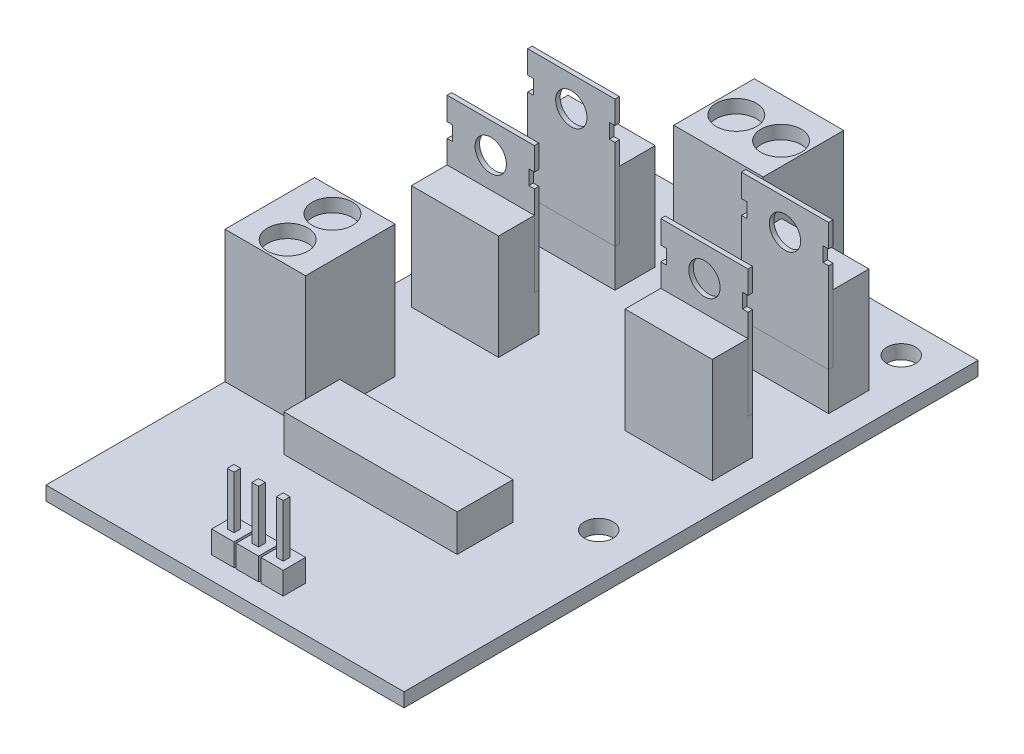
SolidWorks part; units mm, degrees
ref_plane "Front Plane" through (0, 0, 0) normal (0, 0, 1) x (1, 0, 0)
ref_plane "Top Plane" through (0, 0, 0) normal (0, 1, 0) x (1, 0, 0)
ref_plane "Right Plane" through (0, 0, 0) normal (1, 0, 0) x (0, 0, -1)
sketch "Sketch1" plane through (0, 0, 0) normal (0, 1, 0) x (1, 0, 0)
  line L1 (20.32, -32.5755) -> (-20.32, -32.5755)
  line L2 (20.32, -32.5755) -> (20.32, 32.5755)
  line L3 (20.32, 32.5755) -> (-20.32, 32.5755)
  line L4 (-20.32, -32.5755) -> (-20.32, 32.5755)
  line L5 (20.32, -32.5755) -> (-20.32, 32.5755) construction
  line L6 (20.32, 32.5755) -> (-20.32, -32.5755) construction
  point P0 (0, 0)
  dimension "D1" = 40.64
  dimension "D2" = 65.151
extrude "Boss-Extrude1" add sketch "Sketch1" along normal blind 1.5875
sketch "Sketch2" plane through (0, 1.5875, 0) normal (0, 1, 0) x (1, 0, 0)
  line L0 (20.32, 32.5755) -> (-20.32, 32.5755) construction
  line L1 (20.32, -32.5755) -> (20.32, 32.5755) construction
  circle A0 centre (-15.0114, 28.7147) radius 1.6256
  circle A1 centre (15.4686, 28.7147) radius 1.6256
  circle A2 centre (15.4686, -5.6261) radius 1.6256
  dimension "D1" = 30.48
  dimension "D2" = 2.2352
  dimension "D3" = 3.2512
  dimension "D4" = 3.2258
  dimension "D5" = 34.3408
extrude "Cut-Extrude1" cut sketch "Sketch2" against normal through all
sketch "Sketch3" plane through (0, 1.5875, 0) normal (0, 1, 0) x (1, 0, 0)
  line L0 (-5.08, 32.5755) -> (0, 23.4315) construction
  line L1 (-5.08, 32.5755) -> (5.08, 32.5755)
  line L2 (-5.08, 32.5755) -> (-5.08, 23.4315)
  line L3 (-5.08, 23.4315) -> (5.08, 23.4315)
  line L4 (5.08, 32.5755) -> (5.08, 23.4315)
  line L5 (0, 23.4315) -> (5.08, 32.5755) construction
  line L6 (20.32, 32.5755) -> (-20.32, 32.5755) construction
  line L7 (-20.32, 32.5755) -> (-20.32, -32.5755) construction
  line L8 (-20.32, -2.0955) -> (-11.176, -2.0955)
  line L9 (-20.32, -2.0955) -> (-20.32, -12.2555)
  line L10 (-20.32, -12.2555) -> (-11.176, -12.2555)
  line L11 (-11.176, -2.0955) -> (-11.176, -12.2555)
  line L12 (-20.32, -2.0955) -> (-11.176, -7.1755) construction
  line L13 (-11.176, -7.1755) -> (-20.32, -12.2555) construction
  line L14 (-20.32, -32.5755) -> (20.32, -32.5755) construction
  circle A0 centre (-2.54, 28.0035) radius 2.286
  circle A1 centre (2.54, 28.0035) radius 2.286
  circle A2 centre (-15.748, -4.6355) radius 2.286
  circle A3 centre (-15.748, -9.7155) radius 2.286
  line M4 (-20.32, 32.5755) -> (-20.32, -32.5755)
  line M7 (20.32, 32.5755) -> (-20.32, 32.5755)
  dimension "D3" = 4.572
  dimension "D1" = 10.16
  dimension "D2" = 9.144
  dimension "D4" = 20.32
extrude "Boss-Extrude2" add sketch "Sketch3" along normal blind 14.986 separate body contours A2 | L11 L8 L10 A3 A2 M4 | A3 | L4 L2 L3 A1 A0 M7 | A1 | A0 region at (0, 1.5875, -28.0035) region at (-15.748, 1.5875, 7.1755) region at (-2.54, 1.5875, -28.0035) region at (2.54, 1.5875, -28.0035) region at (-15.748, 1.5875, 4.6355) region at (-15.748, 1.5875, 9.7155)
extrude "Cut-Extrude2" cut sketch "Sketch3<3>" against normal blind 1.524 from vertex contours A3 | A2 | A1 | A0 region at (-2.54, 1.5875, -28.0035) region at (2.54, 1.5875, -28.0035) region at (-15.748, 1.5875, 4.6355) region at (-15.748, 1.5875, 9.7155) starting at point (-5.08, 16.5735, -32.5755)
sketch "Sketch3<3>" plane through (0, 1.5875, 0) normal (0, 1, 0) x (1, 0, 0) same geometry as "Sketch3"
sketch "Sketch4" plane through (0, 1.5875, 0) normal (0, 1, 0) x (1, 0, 0)
  line L0 (-7.1755, 23.4315) -> (7.1755, 23.4315) construction
  line L1 (17.0815, 23.4315) -> (7.1755, 23.4315)
  line L2 (17.0815, 23.4315) -> (17.0815, 18.8595)
  line L3 (17.0815, 18.8595) -> (7.1755, 18.8595)
  line L4 (7.1755, 23.4315) -> (7.1755, 18.8595)
  line L5 (17.0815, 5.6515) -> (7.1755, 5.6515)
  line L6 (17.0815, 5.6515) -> (17.0815, 10.2235)
  line L7 (17.0815, 10.2235) -> (7.1755, 10.2235)
  line L8 (7.1755, 5.6515) -> (7.1755, 10.2235)
  line L9 (-17.0815, 5.6515) -> (-7.1755, 5.6515)
  line L10 (-17.0815, 5.6515) -> (-17.0815, 10.2235)
  line L11 (-17.0815, 10.2235) -> (-7.1755, 10.2235)
  line L12 (-7.1755, 5.6515) -> (-7.1755, 10.2235)
  line L13 (-17.0815, 23.4315) -> (-7.1755, 23.4315)
  line L14 (-17.0815, 23.4315) -> (-17.0815, 18.8595)
  line L15 (-17.0815, 18.8595) -> (-7.1755, 18.8595)
  line L16 (-7.1755, 23.4315) -> (-7.1755, 18.8595)
  line L17 (-5.08, 23.4315) -> (5.08, 23.4315) construction
  line L18 (-7.1755, 18.8595) -> (7.1755, 10.2235) construction
  point P16 (0, 23.4315)
  point P20 (0, 14.5415)
  dimension "D1" = 4.572
  dimension "D2" = 9.906
  dimension "D3" = 8.636
  dimension "D4" = 14.351
extrude "Boss-Extrude3" add sketch "Sketch4" along normal blind 11.938 separate body contours L16 L13 L14 L15 region at (-12.1285, 1.5875, -21.1455)
sketch "Sketch5" plane through (0, 0, -18.8595) normal (0, 0, 1) x (1, 0, 0)
  line L0 (-7.1755, 13.5255) -> (-7.1755, 1.5875) construction
  line L1 (-7.1755, 5.9055) -> (-17.0815, 5.9055)
  line L2 (-7.1755, 5.9055) -> (-7.1755, 20.3835)
  line L3 (-7.1755, 20.3835) -> (-17.0815, 20.3835)
  line L4 (-17.0815, 5.9055) -> (-17.0815, 20.3835)
  line L5 (-17.0815, 13.5255) -> (-17.0815, 1.5875) construction
  line L6 (-17.0815, 13.5255) -> (-7.1755, 13.5255) construction
  line L7 (-17.0815, 20.3835) -> (-7.1755, 13.5255) construction
  line L9 (-7.1755, 17.78) -> (-7.8105, 17.78)
  line L10 (-7.1755, 17.78) -> (-7.1755, 16.129)
  line L11 (-7.1755, 16.129) -> (-7.8105, 16.129)
  line L12 (-7.8105, 17.78) -> (-7.8105, 16.129)
  line L13 (-17.0815, 17.78) -> (-16.4465, 17.78)
  line L14 (-17.0815, 17.78) -> (-17.0815, 16.129)
  line L15 (-17.0815, 16.129) -> (-16.4465, 16.129)
  line L16 (-16.4465, 17.78) -> (-16.4465, 16.129)
  circle A0 centre (-12.1285, 16.9545) radius 1.778
  point P22 (-7.8105, 16.9545)
  point P23 (-16.4465, 16.9545)
  line M2 (-7.1755, 1.5875) -> (-7.1755, 13.5255)
  line M3 (-7.1755, 13.5255) -> (-17.0815, 13.5255)
  line M4 (-17.0815, 13.5255) -> (-17.0815, 1.5875)
  dimension "D3" = 3.556
  dimension "D1" = 7.62
  dimension "D2" = 6.858
  dimension "D4" = 0.635
  dimension "D5" = 1.651
extrude "Boss-Extrude4" add sketch "Sketch5" against normal blind 0.508 separate body contours L7 L4 L13 L16 L15 A0 M3 | L3 L7 A0 L2 L11 L12 L9 | L1 M2 M3 M4 region at (-12.1285, 9.7155, -18.8595) region at (-10.3724, 18.2332, -18.8595) region at (-13.8846, 15.6758, -18.8595)
extrude "Cut-Extrude3" cut sketch "Sketch5<3>" against normal up to surface (0.508 mm away) contours L1 M2 M3 M4 region at (-12.1285, 9.7155, -18.8595) up to face at (-10.3505, 16.9545, -19.3675)
sketch "Sketch5<3>" plane through (0, 0, -18.8595) normal (0, 0, 1) x (1, 0, 0) same geometry as "Sketch5"
mirror "Mirror5" about plane through (0, 0, 0) normal (1, 0, 0) of bodies 109 108
ref_plane "Plane1" through (0, 0, -14.5415) normal (0, 0, 1) x (1, 0, 0)
mirror "Mirror6" about plane through (0, 0, -14.5415) normal (0, 0, 1) of bodies 109 108 114 113
sketch "Sketch6" plane through (0, 1.5875, 0) normal (0, 1, 0) x (1, 0, 0)
  line L0 (-20.32, -32.5755) -> (20.32, -32.5755) construction
  line L1 (1.27, -30.0355) -> (-1.27, -30.0355)
  line L2 (1.27, -30.0355) -> (1.27, -27.4955)
  line L3 (1.27, -27.4955) -> (-1.27, -27.4955)
  line L4 (-1.27, -30.0355) -> (-1.27, -27.4955)
  line L5 (1.27, -30.0355) -> (-1.27, -27.4955) construction
  line L6 (1.27, -27.4955) -> (-1.27, -30.0355) construction
  line L7 (4.064, -30.0355) -> (1.524, -30.0355)
  line L8 (4.064, -30.0355) -> (4.064, -27.4955)
  line L9 (4.064, -27.4955) -> (1.524, -27.4955)
  line L10 (1.524, -30.0355) -> (1.524, -27.4955)
  line L11 (4.064, -30.0355) -> (1.524, -27.4955) construction
  line L12 (4.064, -27.4955) -> (1.524, -30.0355) construction
  line L13 (-1.524, -30.0355) -> (-4.064, -30.0355)
  line L14 (-1.524, -30.0355) -> (-1.524, -27.4955)
  line L15 (-1.524, -27.4955) -> (-4.064, -27.4955)
  line L16 (-4.064, -30.0355) -> (-4.064, -27.4955)
  line L17 (-1.524, -30.0355) -> (-4.064, -27.4955) construction
  line L18 (-1.524, -27.4955) -> (-4.064, -30.0355) construction
  point P0 (0, -28.7655)
  point P5 (2.794, -28.7655)
  point P10 (-2.794, -28.7655)
  dimension "D1" = 0.254
  dimension "D2" = 0.254
  dimension "D3" = 2.54
  dimension "D4" = 2.54
extrude "Boss-Extrude5" add sketch "Sketch6" along normal blind 2.54
sketch "Sketch7" plane through (0, 4.1275, 0) normal (0, 1, 0) x (1, 0, 0)
  line L12 (-3.175, -28.3845) -> (-3.175, -29.1465)
  line L13 (-3.175, -29.1465) -> (-2.413, -29.1465)
  line L14 (-2.413, -29.1465) -> (-2.413, -28.3845)
  line L15 (-2.413, -28.3845) -> (-3.175, -28.3845)
  line L16 (-3.175, -28.3845) -> (-3.175, -29.1465)
  line L17 (-3.175, -29.1465) -> (-2.413, -29.1465)
  line L18 (-2.413, -29.1465) -> (-2.413, -28.3845)
  line L19 (-2.413, -28.3845) -> (-3.175, -28.3845)
  line L24 (-0.381, -28.3845) -> (-0.381, -29.1465)
  line L25 (-0.381, -29.1465) -> (0.381, -29.1465)
  line L26 (0.381, -29.1465) -> (0.381, -28.3845)
  line L27 (0.381, -28.3845) -> (-0.381, -28.3845)
  line L28 (-0.381, -28.3845) -> (-0.381, -29.1465)
  line L29 (-0.381, -29.1465) -> (0.381, -29.1465)
  line L30 (0.381, -29.1465) -> (0.381, -28.3845)
  line L31 (0.381, -28.3845) -> (-0.381, -28.3845)
  line L36 (2.413, -28.3845) -> (2.413, -29.1465)
  line L37 (2.413, -29.1465) -> (3.175, -29.1465)
  line L38 (3.175, -29.1465) -> (3.175, -28.3845)
  line L39 (3.175, -28.3845) -> (2.413, -28.3845)
  line L40 (2.413, -28.3845) -> (2.413, -29.1465)
  line L41 (2.413, -29.1465) -> (3.175, -29.1465)
  line L42 (3.175, -29.1465) -> (3.175, -28.3845)
  line L43 (3.175, -28.3845) -> (2.413, -28.3845)
  dimension "D1" = 0.889
  dimension "D2" = 0.889
  dimension "D3" = 0.889
extrude "Boss-Extrude6" add sketch "Sketch7" along normal blind 5.969
sketch "Sketch8" plane through (0, 1.5875, 0) normal (0, 1, 0) x (1, 0, 0)
  line L0 (-20.32, -32.5755) -> (20.32, -32.5755) construction
  line L1 (9.8425, -16.0655) -> (-9.8425, -16.0655)
  line L2 (9.8425, -16.0655) -> (9.8425, -9.7155)
  line L3 (9.8425, -9.7155) -> (-9.8425, -9.7155)
  line L4 (-9.8425, -16.0655) -> (-9.8425, -9.7155)
  line L5 (9.8425, -16.0655) -> (-9.8425, -9.7155) construction
  line L6 (9.8425, -9.7155) -> (-9.8425, -16.0655) construction
  point P0 (0, -12.8905)
  dimension "D1" = 6.35
  dimension "D2" = 19.685
  dimension "D3" = 16.51
extrude "Boss-Extrude7" add sketch "Sketch8" along normal blind 4.191
